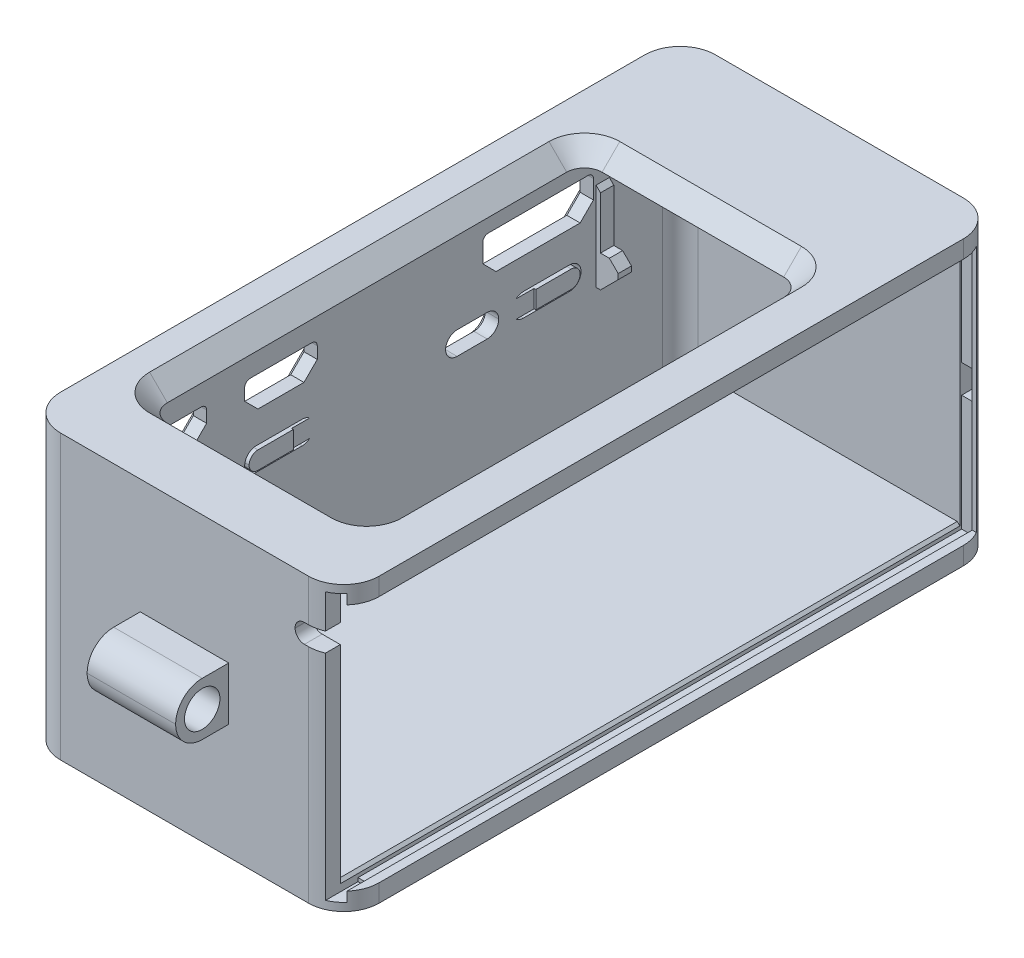
SolidWorks part; units mm, degrees
ref_plane "前视基准面" through (0, 0, 0) normal (0, 0, 1) x (1, 0, 0)
ref_plane "上视基准面" through (0, 0, 0) normal (0, 1, 0) x (1, 0, 0)
ref_plane "右视基准面" through (0, 0, 0) normal (1, 0, 0) x (0, 0, -1)
sketch "草图1" plane through (0, 0, 0) normal (1, 0, 0) x (0, 0, -1)
  line L1 (-54.0501, 29.0398) -> (19.9499, 29.0398)
  line L2 (-54.0501, 29.0398) -> (-54.0501, -2.9602)
  line L3 (-54.0501, -2.9602) -> (19.9499, -2.9602)
  line L4 (19.9499, 29.0398) -> (19.9499, -2.9602)
  dimension "D1" = 74
  dimension "D2" = 32
extrude "凸台-拉伸1" add sketch "草图1" along normal blind 36
sketch "草图2" plane through (36, 0, 0) normal (1, 0, 0) x (0, 0, -1)
  line L8 (17.9499, -0.9602) -> (17.9499, 27.0398)
  line L9 (-52.0501, -0.9602) -> (17.9499, -0.9602)
  line L10 (-52.0501, 27.0398) -> (-52.0501, -0.9602)
  line L11 (17.9499, 27.0398) -> (-52.0501, 27.0398)
  line L12 (17.9499, -0.9602) -> (17.9499, 27.0398)
  line L13 (-52.0501, -0.9602) -> (17.9499, -0.9602)
  line L14 (-52.0501, 27.0398) -> (-52.0501, -0.9602)
  line L15 (17.9499, 27.0398) -> (-52.0501, 27.0398)
  dimension "D1" = 2
extrude "切除-拉伸1" cut sketch "草图2" against normal blind 34
fillet "圆角1" radius 2 2 edges at (2, 13.0398, -17.9499) (2, 13.0398, 52.0501)
fillet "圆角2" radius 4 4 edges at (0, 13.0398, -19.9499) (0, 13.0398, 54.0501) (36, 13.0398, 54.0501) (36, 13.0398, -19.9499)
sketch "草图3" plane through (0, 29.0398, 0) normal (0, 1, 0) x (1, 0, 0)
  line L0 (32, 19.9499) -> (4, 19.9499) construction
  line L1 (29.59, 4.0599) -> (5.07, 4.0599)
  line L2 (29.59, 4.0599) -> (29.59, -45.0601)
  line L3 (29.59, -45.0601) -> (5.07, -45.0601)
  line L4 (5.07, 4.0599) -> (5.07, -45.0601)
  line L5 (36, 15.9499) -> (36, -50.0501) construction
  line L6 (32, -54.0501) -> (4, -54.0501) construction
  line L7 (0, 15.9499) -> (0, -50.0501) construction
  dimension "D1" = 15.89
  dimension "D2" = 6.41
  dimension "D3" = 8.99
  dimension "D4" = 5.07
extrude "切除-拉伸2" cut sketch "草图3" against normal blind 10
fillet "圆角3" radius 2 4 edges at (5.07, 28.0398, 45.0601) (29.59, 28.0398, 45.0601) (29.59, 28.0398, -4.0599) (5.07, 28.0398, -4.0599)
chamfer "倒角1" distance 2 angle 45 8 edges at (17.33, 29.0398, 45.0601) (29.0042, 29.0398, 44.4744) (5.6558, 29.0398, 44.4744) (29.59, 29.0398, 20.5001) (5.07, 29.0398, 20.5001) (29.0042, 29.0398, -3.4741) (5.6558, 29.0398, -3.4741) (17.33, 29.0398, -4.0599)
sketch "草图4" plane through (0, 0, 0) normal (-1, 0, 0) x (0, 0, 1)
  line L0 (-15.9499, 29.0398) -> (50.0501, 29.0398) construction
  line L1 (-8.1499, 22.4398) -> (4.3501, 22.4398)
  line L2 (-8.1499, 22.4398) -> (-8.1499, 18.2398)
  line L3 (-8.1499, 18.2398) -> (4.3501, 18.2398)
  line L4 (4.3501, 22.4398) -> (4.3501, 18.2398)
  line L5 (23.0501, 21.6812) -> (31.2501, 21.6812)
  line L6 (23.0501, 21.6812) -> (23.0501, 18.2398)
  line L7 (23.0501, 18.2398) -> (31.2501, 18.2398)
  line L8 (31.2501, 21.6812) -> (31.2501, 18.2398)
  line L9 (35.5501, 21.6398) -> (43.7501, 21.6398)
  line L10 (35.5501, 21.6398) -> (35.5501, 18.2398)
  line L11 (35.5501, 18.2398) -> (43.7501, 18.2398)
  line L12 (43.7501, 21.6398) -> (43.7501, 18.2398)
  line L13 (-6.7499, 14.7398) -> (1.0501, 14.7398)
  line L14 (-6.7499, 14.7398) -> (-6.7499, 12.1398)
  line L15 (-6.7499, 12.1398) -> (1.0501, 12.1398)
  line L16 (1.0501, 14.7398) -> (1.0501, 12.1398)
  line L17 (23.4501, 14.7398) -> (31.2501, 14.7398)
  line L18 (23.4501, 14.7398) -> (23.4501, 12.1398)
  line L19 (23.4501, 12.1398) -> (31.2501, 12.1398)
  line L20 (31.2501, 14.7398) -> (31.2501, 12.1398)
  line L21 (33.8696, 14.7398) -> (43.3696, 14.7398)
  line L22 (33.8696, 14.7398) -> (33.8696, 11.5398)
  line L23 (33.8696, 11.5398) -> (43.3696, 11.5398)
  line L24 (43.3696, 14.7398) -> (43.3696, 11.5398)
  line L25 (54.0501, 29.0398) -> (54.0501, -2.9602) construction
  line L27 (8.5501, 14.7398) -> (2.5501, 14.7398)
  line L28 (8.5501, 14.7398) -> (8.5501, 12.1398)
  line L29 (8.5501, 12.1398) -> (2.5501, 12.1398)
  line L30 (2.5501, 14.7398) -> (2.5501, 12.1398)
  dimension "D1" = 14.3
  dimension "D2" = 3.2
  dimension "D3" = 2.6
  dimension "D4" = 7.8
  dimension "D5" = 7.8
  dimension "D6" = 8.2
  dimension "D7" = 8.2
  dimension "D8" = 3.4
  dimension "D9" = 12.5
  dimension "D10" = 4.2
  dimension "D11" = 10.8
  dimension "D12" = 10.3
  dimension "D13" = 4.3
  dimension "D14" = 18.7
  dimension "D15" = 9.5
  dimension "D16" = 53
  dimension "D17" = 1.5
  dimension "D18" = 6
extrude "切除-拉伸3" cut sketch "草图4" against normal blind 10
fillet "圆角8" radius 1.3 4 edges at (1, 14.7398, 2.5501) (1, 14.7398, 8.5501) (1, 12.1398, 8.5501) (1, 12.1398, 2.5501)
sketch "草图5" plane through (2, 0, 0) normal (1, 0, 0) x (0, 0, -1)
  line L0 (-23.4501, 12.1398) -> (-23.4501, 14.7398) construction
  line L1 (-23.4501, 14.4398) -> (-30.9501, 14.4398)
  line L2 (-23.4501, 14.4398) -> (-23.4501, 12.4398)
  line L3 (-23.4501, 12.4398) -> (-30.9501, 12.4398)
  line L4 (-30.9501, 14.4398) -> (-30.9501, 12.4398)
  line L5 (-1.0501, 14.7398) -> (-1.0501, 12.1398) construction
  line L6 (-1.0501, 12.4398) -> (6.4499, 12.4398)
  line L7 (-1.0501, 12.4398) -> (-1.0501, 14.4398)
  line L8 (-1.0501, 14.4398) -> (6.4499, 14.4398)
  line L9 (6.4499, 12.4398) -> (6.4499, 14.4398)
  line L10 (-23.4501, 14.7398) -> (-31.2501, 14.7398) construction
  line L11 (-31.2501, 12.1398) -> (-23.4501, 12.1398) construction
  line L12 (-31.2501, 14.7398) -> (-31.2501, 12.1398) construction
  line L13 (6.7499, 14.7398) -> (-1.0501, 14.7398) construction
  line L14 (-1.0501, 12.1398) -> (6.7499, 12.1398) construction
  line L15 (6.7499, 12.1398) -> (6.7499, 14.7398) construction
  dimension "D1" = 0.3
  dimension "D2" = 0.3
  dimension "D3" = 0.3
  dimension "D4" = 0.3
  dimension "D5" = 0.3
  dimension "D6" = 0.3
extrude "凸台-拉伸2" add sketch "草图5" against normal blind 1.2
sketch "草图6" plane through (0.8, 0, 0) normal (-1, 0, 0) x (0, 0, 1)
  line L0 (1.0501, 12.4398) -> (-6.4499, 12.4398) construction
  line L1 (-6.4499, 14.4398) -> (-1.4499, 14.4398)
  line L2 (-6.4499, 14.4398) -> (-6.4499, 12.4398)
  line L3 (-6.4499, 12.4398) -> (-1.4499, 12.4398)
  line L4 (-1.4499, 14.4398) -> (-1.4499, 12.4398)
  line L5 (30.9501, 12.4398) -> (23.4501, 12.4398) construction
  line L6 (30.9501, 14.4398) -> (25.9501, 14.4398)
  line L7 (30.9501, 14.4398) -> (30.9501, 12.4398)
  line L8 (30.9501, 12.4398) -> (25.9501, 12.4398)
  line L9 (25.9501, 14.4398) -> (25.9501, 12.4398)
  dimension "D1" = 5
  dimension "D2" = 5
extrude "凸台-拉伸3" add sketch "草图6" along normal blind 1.5 and the other way blind 1.4
fillet "圆角4" radius 0.6 10 edges at (1, 11.5398, 33.8696) (1, 14.7398, 33.8696) (1, 14.7398, 43.3696) (1, 11.5398, 43.3696) (1, 21.6398, 35.5501) (1, 21.6398, 43.7501) (1, 21.6812, 31.2501) (1, 21.6812, 23.0501) (1, 22.4398, -8.1499) (1, 22.4398, 4.3501)
chamfer "倒角2" distance 1.5 angle 45 6 edges at (1, 18.2398, 43.7501) (1, 18.2398, 35.5501) (1, 18.2398, 31.2501) (1, 18.2398, 23.0501) (1, 18.2398, 4.3501) (1, 18.2398, -8.1499)
fillet "圆角5" radius 1 8 edges at (0.05, 12.4398, 25.9501) (0.05, 14.4398, 25.9501) (0.75, 12.4398, 30.9501) (0.75, 14.4398, 30.9501) (0.05, 12.4398, -1.4499) (0.05, 14.4398, -1.4499) (0.75, 12.4398, -6.4499) (0.75, 14.4398, -6.4499)
chamfer "倒角10" distance 0.2 angle 45 12 edges at (-0.7, 12.4398, 28.4501) (-0.7, 12.7327, 30.6572) (-0.7, 12.7327, 26.243) (-0.7, 14.1469, 30.6572) (-0.7, 14.1469, 26.243) (-0.7, 14.4398, 28.4501) (-0.7, 12.4398, -3.9499) (-0.7, 12.7327, -1.7428) (-0.7, 12.7327, -6.157) (-0.7, 14.1469, -1.7428) (-0.7, 14.1469, -6.157) (-0.7, 14.4398, -3.9499)
fillet "圆角6" radius 1.3 8 edges at (1, 14.7398, 1.0501) (1, 12.1398, 1.0501) (1, 12.1398, -6.7499) (1, 14.7398, -6.7499) (1, 14.7398, 23.4501) (1, 12.1398, 23.4501) (1, 12.1398, 31.2501) (1, 14.7398, 31.2501)
chamfer "倒角4" distance 0.5 angle 45 50 edges at (0, 12.1398, -2.8499) (0, 12.5206, 0.6694) (0, 12.5206, -6.3691) (0, 14.359, 0.6694) (0, 14.359, -6.3691) (0, 14.7398, -2.8499) (0, 18.9898, -7.3999) (0, 18.2398, -1.8999) (0, 18.9898, 3.6001) (0, 20.7898, 4.3501) (0, 20.7898, -8.1499) (0, 22.2641, 4.1744) (0, 22.2641, -7.9741) (0, 22.4398, -1.8999) (0, 11.5398, 38.6196) (0, 11.7155, 43.1938) (0, 11.7155, 34.0453) (0, 13.1398, 43.3696) (0, 13.1398, 33.8696) (0, 14.5641, 43.1938) (0, 14.5641, 34.0453) (0, 14.7398, 38.6196) (0, 12.1398, 27.3501) (0, 12.5206, 30.8694) (0, 12.5206, 23.8309) (0, 14.359, 30.8694) (0, 14.359, 23.8309) (0, 14.7398, 27.3501) (0, 20.4105, 23.0501) (0, 21.5055, 23.2259) (0, 21.6812, 27.1501) (0, 21.5055, 31.0744) (0, 18.9898, 23.8001) (0, 18.2398, 27.1501) (0, 18.9898, 30.5001) (0, 20.4105, 31.2501) (0, 18.9898, 43.0001) (0, 18.2398, 39.6501) (0, 18.9898, 36.3001) (0, 20.3898, 35.5501) (0, 21.4641, 35.7259) (0, 21.6398, 39.6501) (0, 20.3898, 43.7501) (0, 21.4641, 43.5744) (0, 12.5206, 8.1694) (0, 12.1398, 5.5501) (0, 12.5206, 2.9309) (0, 14.359, 8.1694) (0, 14.7398, 5.5501) (0, 14.359, 2.9309)
sketch "草图7" plane through (2, 0, 0) normal (1, 0, 0) x (0, 0, -1)
  line L0 (15.9499, 27.0398) -> (-50.0501, 27.0398) construction
  line L1 (-46.0501, 21.0398) -> (-44.5501, 21.0398)
  line L2 (-46.0501, 21.0398) -> (-46.0501, 11.0398)
  line L3 (-46.0501, 11.0398) -> (-44.5501, 11.0398)
  line L4 (-44.5501, 21.0398) -> (-44.5501, 11.0398)
  line L5 (8.4499, 21.0398) -> (9.9499, 21.0398)
  line L6 (8.4499, 21.0398) -> (8.4499, 11.0398)
  line L7 (8.4499, 11.0398) -> (9.9499, 11.0398)
  line L8 (9.9499, 21.0398) -> (9.9499, 11.0398)
  line L11 (17.9499, -0.9602) -> (17.9499, 27.0398) construction
  line L12 (-52.0501, 27.0398) -> (-52.0501, -0.9602) construction
  dimension "D1" = 6
  dimension "D2" = 10
  dimension "D3" = 1.5
  dimension "D4" = 1.5
  dimension "D5" = 8
  dimension "D6" = 6
extrude "凸台-拉伸4" add sketch "草图7" along normal blind 0.5
sketch "草图10" plane through (2.5, 0, 0) normal (1, 0, 0) x (0, 0, -1)
  line L1 (-46.0501, 11.0398) -> (-44.5501, 11.0398)
  line L2 (-46.0501, 11.0398) -> (-46.0501, 14.6398)
  line L3 (-46.0501, 14.6398) -> (-44.5501, 14.6398)
  line L4 (-44.5501, 11.0398) -> (-44.5501, 14.6398)
  line L7 (8.4499, 11.0398) -> (9.9499, 11.0398)
  line L8 (8.4499, 11.0398) -> (8.4499, 14.6398)
  line L9 (8.4499, 14.6398) -> (9.9499, 14.6398)
  line L10 (9.9499, 11.0398) -> (9.9499, 14.6398)
  dimension "D1" = 3.6
extrude "凸台-拉伸6" add sketch "草图10" along normal blind 2
chamfer "倒角7" distance 1 angle 45 2 edges at (4.5, 14.6398, -9.1999) (4.5, 14.6398, 45.3001)
chamfer "倒角8" distance 2 angle 45 2 edges at (4.5, 11.0398, 45.3001) (4.5, 11.0398, -9.1999)
chamfer "倒角5" distance 0.5 angle 45 2 edges at (2.5, 21.0398, 45.3001) (2.5, 21.0398, -9.1999)
sketch "草图8" plane through (2, 0, 0) normal (1, 0, 0) x (0, 0, -1)
  line L1 (-52.0501, 22.2398) -> (-48.0501, 22.2398)
  line L2 (-52.0501, 22.2398) -> (-52.0501, 24.2398)
  line L3 (-52.0501, 24.2398) -> (-48.0501, 24.2398)
  line L4 (-48.0501, 22.2398) -> (-48.0501, 24.2398)
  line L6 (17.9499, 24.2398) -> (11.9499, 24.2398)
  line L7 (17.9499, 24.2398) -> (17.9499, 22.2398)
  line L8 (17.9499, 22.2398) -> (11.9499, 22.2398)
  line L9 (11.9499, 24.2398) -> (11.9499, 22.2398)
  line L10 (15.9499, 27.0398) -> (-50.0501, 27.0398) construction
  line L11 (17.9499, -0.9602) -> (17.9499, 27.0398) construction
  line L12 (-52.0501, 27.0398) -> (-52.0501, -0.9602) construction
  dimension "D1" = 2.8
  dimension "D2" = 2
  dimension "D3" = 4
  dimension "D4" = 6
extrude "凸台-拉伸5" add sketch "草图8" along normal blind 3
chamfer "倒角6" distance 1 angle 45 2 edges at (5, 24.2398, -14.9499) (5, 24.2398, 50.0501)
sketch "草图12" plane through (0, 0, 54.0501) normal (0, 0, 1) x (1, 0, 0)
  line L0 (4, -0.9602) -> (35.4641, -0.9602) construction
  line L1 (36, 27.0398) -> (33.6, 27.0398)
  line L2 (36, 27.0398) -> (36, -0.9602)
  line L3 (36, -0.9602) -> (33.6, -0.9602)
  line L4 (33.6, 27.0398) -> (33.6, -0.9602)
  dimension "D1" = 2.4
extrude "切除-拉伸5" cut sketch "草图12" against normal blind 10.8
sketch "草图11" plane through (0, -0.9602, 0) normal (0, 1, 0) x (1, 0, 0)
  line L0 (32, 19.9499) -> (4, 19.9499) construction
  line L1 (35, 17.9499) -> (33.6, 17.9499)
  line L2 (35, 17.9499) -> (35, -54.0501)
  line L3 (35, -54.0501) -> (33.6, -54.0501)
  line L4 (33.6, 17.9499) -> (33.6, -54.0501)
  line L5 (32, -54.0501) -> (4, -54.0501) construction
  line L6 (36, -50.0501) -> (36, 15.9499) construction
  dimension "D1" = 2
  dimension "D2" = 0
  dimension "D3" = 1
  dimension "D4" = 1.4
extrude "切除-拉伸4" cut sketch "草图11" against normal blind 0.7
sketch "草图13" plane through (0, 27.0398, 0) normal (0, -1, 0) x (1, 0, 0)
  line L10 (33.6, -17.9499) -> (35, -17.9499)
  line L11 (33.6, 54.0501) -> (33.6, -17.9499)
  line L12 (35, 54.0501) -> (33.6, 54.0501)
  line L13 (35, -17.9499) -> (35, 54.0501)
  line L14 (33.6, -17.9499) -> (35, -17.9499)
  line L15 (33.6, 54.0501) -> (33.6, -17.9499)
  line L16 (35, 54.0501) -> (33.6, 54.0501)
  line L17 (35, -17.9499) -> (35, 54.0501)
  dimension "D1" = 0
extrude "切除-拉伸6" cut sketch "草图13" against normal blind 0.7
sketch "草图14" plane through (0, -1.6602, 0) normal (0, 1, 0) x (1, 0, 0)
  line L1 (33.6, -54.0501) -> (35, -54.0501)
  line L2 (33.6, -54.0501) -> (33.6, -50.0501)
  line L3 (33.6, -50.0501) -> (35, -50.0501)
  line L4 (35, -54.0501) -> (35, -50.0501)
  line L5 (32, -54.0501) -> (4, -54.0501) construction
  line L6 (33.6, -53.7162) -> (33.6, 17.9499) construction
  dimension "D1" = 4
extrude "切除-拉伸7" cut sketch "草图14" against normal blind 0.4
sketch "草图15" plane through (0, 27.7398, 0) normal (0, -1, 0) x (1, 0, 0)
  line L3 (35, 50.0501) -> (35, 52.6959)
  line L4 (33.6, 50.0501) -> (35, 50.0501)
  line L5 (33.6, 53.7162) -> (33.6, 50.0501)
  line L7 (33.6, 50.0501) -> (35, 50.0501)
  line L8 (33.6, 53.7162) -> (33.6, 50.0501)
  line L10 (35, 50.0501) -> (35, 52.6959)
  arc A1 (35, 52.6959) -> (33.6, 53.7162) centre (32, 50.0501) ccw
  arc A2 (35, 52.6959) -> (33.6, 53.7162) centre (32, 50.0501) ccw
  dimension "D1" = 0
extrude "切除-拉伸8" cut sketch "草图15" against normal blind 0.4
sketch "草图16" plane through (0, 0, -17.9499) normal (0, 0, 1) x (1, 0, 0)
  line L0 (33.6, 28.1398) -> (33.6, -2.0602) construction
  line L1 (33.6, 27.7398) -> (35, 27.7398)
  line L2 (33.6, 27.7398) -> (33.6, -1.6602)
  line L3 (33.6, -1.6602) -> (35, -1.6602)
  line L4 (35, 27.7398) -> (35, -1.6602)
extrude "切除-拉伸9" cut sketch "草图16" against normal blind 0.2
chamfer "倒角9" distance 0.3 angle 45 2 edges at (33.6, 27.0398, 17.0501) (33.6, -0.9602, 17.0501)
ref_plane "基准面4" through (0, 13.0398, 0) normal (0, -1, 0) x (-1, 0, 0)
sketch "草图19" plane through (0, 0, -18.1499) normal (0, 0, 1) x (1, 0, 0)
  line L0 (35, 13.0398) -> (40.512, 13.0398) construction
  line L1 (35.4641, -0.9602) -> (35.4641, 27.0398) construction
  line L3 (34.3, 27.7398) -> (34.3, 24.7272) construction
  line L4 (33.6, 27.7398) -> (35, 27.7398) construction
  line L5 (35, -0.9602) -> (35, 27.0398) construction
  line L6 (33.6, 14.6398) -> (35, 14.6398)
  line L7 (33.6, 14.6398) -> (33.6, 11.4398)
  line L8 (33.6, 11.4398) -> (35, 11.4398)
  line L9 (35, 14.6398) -> (35, 11.4398)
  line L10 (33.6, 14.6398) -> (35, 11.4398) construction
  line L11 (33.6, 11.4398) -> (35, 14.6398) construction
  point P2 (34.3, 13.0398)
  point P13 (35.4641, 13.0398)
  point P16 (34.3, 27.7398)
  dimension "D1" = 3.2
extrude "切除-拉伸11" cut sketch "草图19" against normal blind 10
sketch "草图20" plane through (0, 0, 54.0501) normal (0, 0, 1) x (1, 0, 0)
  line L0 (33.6, 24.2398) -> (33.6, 28.1198) construction
  line L1 (33.6, 24.2898) -> (30.5, 24.2898)
  line L2 (33.6, 24.2898) -> (33.6, 22.1398)
  line L3 (33.6, 22.1398) -> (30.5, 22.1398)
  line L4 (30.5, 24.2898) -> (30.5, 22.1398)
  line L5 (32, 29.0398) -> (4, 29.0398) construction
  dimension "D1" = 4.75
  dimension "D2" = 2.15
  dimension "D3" = 3.1
extrude "切除-拉伸12" cut sketch "草图20" against normal up to next
fillet "圆角9" radius 1.05 2 edges at (30.5, 24.2898, 53.0501) (30.5, 22.1398, 53.0501)
sketch "草图21" plane through (0, 0, -19.9499) normal (0, 0, -1) x (-1, 0, 0)
  line L0 (-25, 19.5398) -> (-14, 19.5398) construction
  line L1 (-25, 21.0398) -> (-14, 21.0398)
  line L2 (-25, 18.0398) -> (-14, 18.0398)
  line L3 (-4, -2.9602) -> (-4, 29.0398) construction
  line L4 (-32, 29.0398) -> (-4, 29.0398) construction
  arc A0 (-25, 21.0398) -> (-25, 18.0398) centre (-25, 19.5398) ccw
  arc A1 (-14, 18.0398) -> (-14, 21.0398) centre (-14, 19.5398) ccw
  point P2 (-19.5, 19.5398)
  dimension "D4" = 1.5
  dimension "D1" = 10
  dimension "D2" = 9.5
  dimension "D3" = 11
extrude "切除-拉伸13" cut sketch "草图21" against normal up to next
sketch "草图22" plane through (0, -2.9602, 0) normal (0, -1, 0) x (1, 0, 0)
  line L0 (7.07, -6.0599) -> (27.59, -6.0599) construction
  line B0 (12.438, 7.4573) -> (11.965, 6.6368)
  line B1 (11.965, 6.6368) -> (9.5089, 2.3799)
  line B2 (9.5089, 2.3799) -> (9.0302, 1.5593)
  line B3 (9.0302, -0.1617) -> (9.5089, -0.9823)
  line B4 (9.5089, -0.9823) -> (11.965, -5.2392)
  line B5 (11.965, -5.2392) -> (12.438, -6.0599)
  line B6 (13.9253, -6.9204) -> (20.7409, -6.9204)
  line B7 (22.2283, -6.0599) -> (22.7013, -5.2392)
  line B8 (22.7013, -5.2392) -> (25.1574, -0.9823)
  line B9 (25.1574, -0.9823) -> (25.6361, -0.1617)
  line B10 (25.6361, 1.5593) -> (25.1574, 2.3799)
  line B11 (25.1574, 2.3799) -> (22.7013, 6.6368)
  line B12 (22.7013, 6.6368) -> (22.2283, 7.4573)
  line B13 (20.7409, 8.3178) -> (13.9253, 8.3178)
  line B14 (13.1161, -4.9657) -> (10.073, 0.2999)
  line B15 (10.073, 1.1034) -> (13.1218, 6.3404)
  line B16 (13.8228, 6.3461) -> (16.8658, 1.2573)
  line B17 (22.0231, 2.8358) -> (22.3536, 2.2431)
  line B18 (22.4505, 2.1861) -> (24.1601, 2.1861)
  line B19 (24.257, 2.1292) -> (24.8838, 1.0236)
  line B20 (24.787, 0.8583) -> (19.51, 0.8583)
  line B21 (19.4131, 0.9153) -> (18.3475, 2.7959)
  line B22 (21.6698, 6.7393) -> (22.291, 5.6452)
  line B23 (22.1941, 5.4799) -> (19.681, 5.4799)
  line B24 (19.5841, 5.537) -> (18.9686, 6.6311)
  line B25 (19.0655, 6.7963) -> (21.5729, 6.7963)
  line B26 (21.0088, 2.7674) -> (21.2709, 2.2431)
  line B27 (21.1512, 2.1861) -> (19.8064, 2.1861)
  line B28 (19.7095, 2.2431) -> (19.4359, 2.7332)
  line B29 (14.404, 12.3126) -> (14.404, 10.4377)
  line B30 (14.404, 10.4377) -> (20.9689, 10.4377)
  line B31 (20.9689, 10.4377) -> (20.9689, 11.2698)
  line B32 (20.9689, 11.2698) -> (18.3646, 11.2698)
  line B33 (18.3646, 11.2698) -> (18.3646, 12.3582)
  line B34 (17.6921, 12.25) -> (17.6921, 11.2698)
  line B35 (17.6921, 11.2698) -> (15.0765, 11.2698)
  line B36 (15.0765, 11.2698) -> (15.0765, 12.2158)
  line B37 (16.1022, 15.8514) -> (20.9689, 15.8514)
  line B38 (20.9689, 15.8514) -> (20.9689, 16.6665)
  line B39 (20.9689, 16.6665) -> (16.1022, 16.6665)
  line B40 (16.1022, 16.6665) -> (16.1022, 15.8514)
  line B41 (17.1793, 21.3735) -> (16.8487, 20.5415)
  line B42 (16.0623, 21.6983) -> (15.0594, 22.4962)
  line B43 (18.0227, 19.265) -> (18.3817, 20.1141)
  line B44 (19.0313, 18.564) -> (20.1369, 17.658)
  line B45 (15.8743, 26.4795) -> (19.2137, 26.4795)
  line B46 (18.8262, 25.0377) -> (15.8743, 25.0377)
  line B47 (15.8743, 25.0377) -> (15.8743, 23.4478)
  line B48 (15.8743, 23.4478) -> (19.0256, 23.4478)
  line B49 (20.2679, 26.6277) -> (20.2679, 26.6618)
  line B50 (20.2679, 26.6618) -> (20.9689, 26.7759)
  line B51 (20.9689, 26.7759) -> (20.9689, 28.0751)
  line B52 (20.9689, 28.0751) -> (15.8743, 28.0751)
  line B53 (15.8743, 28.0751) -> (15.8743, 26.4795)
  line B54 (19.9659, 31.9274) -> (19.9659, 31.1239)
  line B55 (17.0254, 33.0216) -> (17.0254, 33.8079)
  line B56 (17.0254, 33.8079) -> (15.8743, 33.8079)
  line B57 (15.8743, 33.8079) -> (15.8743, 31.9388)
  line B58 (18.9174, 29.6878) -> (18.9516, 29.6878)
  line B59 (20.7808, 29.591) -> (20.8264, 29.591)
  line B60 (21.1854, 31.141) -> (21.1854, 31.6254)
  line B61 (16.4156, 34.2638) -> (17.4642, 34.8223)
  line B62 (20.456, 37.0676) -> (20.456, 37.1075)
  line B63 (20.456, 37.1075) -> (20.9689, 37.2214)
  line B64 (20.9689, 37.2214) -> (20.9689, 38.5207)
  line B65 (20.9689, 38.5207) -> (18.074, 38.5207)
  line B66 (18.6381, 36.9251) -> (19.453, 36.9251)
  line B67 (16.7576, 41.0111) -> (16.7576, 40.9769)
  line B68 (16.7576, 40.9769) -> (15.8743, 40.8686)
  line B69 (15.8743, 40.8686) -> (15.8743, 39.5693)
  line B70 (15.8743, 39.5693) -> (20.9689, 39.5693)
  line B71 (20.9689, 39.5693) -> (20.9689, 41.1536)
  line B72 (20.9689, 41.1536) -> (18.0569, 41.1536)
  line B73 (17.2248, 42.8118) -> (15.8515, 43.0796)
  line B74 (21.2709, 2.2431) -> (22.3536, 2.2431)
  line B75 (21.1512, 2.1861) -> (22.4505, 2.1861)
  spline B76 degree 3 poles (9.0302, 1.5593) (8.882, 1.2914) (8.8022, 0.9951) (8.8022, 0.6988) knots 3 3 3 3 4 4 4 4
  spline B77 degree 3 poles (8.8022, 0.6988) (8.8022, 0.4025) (8.882, 0.1061) (9.0302, -0.1617) knots 4 4 4 4 5 5 5 5
  spline B78 degree 3 poles (12.438, -6.0599) (12.7457, -6.5898) (13.3156, -6.9204) (13.9253, -6.9204) knots 8 8 8 8 9 9 9 9
  spline B79 degree 3 poles (20.7409, -6.9204) (21.3564, -6.9204) (21.9206, -6.5898) (22.2283, -6.0599) knots 10 10 10 10 11 11 11 11
  spline B80 degree 3 poles (25.6361, -0.1617) (25.7899, 0.1061) (25.864, 0.4025) (25.864, 0.6988) knots 14 14 14 14 15 15 15 15
  spline B81 degree 3 poles (25.864, 0.6988) (25.864, 0.9951) (25.7899, 1.2914) (25.6361, 1.5593) knots 15 15 15 15 16 16 16 16
  spline B82 degree 3 poles (22.2283, 7.4573) (21.9206, 7.993) (21.3564, 8.3178) (20.7409, 8.3178) knots 19 19 19 19 20 20 20 20
  spline B83 degree 3 poles (13.9253, 8.3178) (13.3156, 8.3178) (12.7457, 7.993) (12.438, 7.4573) knots 21 21 21 21 22 22 22 22
  spline B84 degree 2 poles (16.8658, 0.146) (13.8911, -5.0056) (13.8854, -5.017) knots 0 0 0 1 1 1
  spline B85 degree 3 poles (13.8854, -5.017) (13.6917, -5.2848) (13.2814, -5.2563) (13.1161, -4.9657) knots 1 1 1 1 2 2 2 2
  spline B86 degree 3 poles (10.073, 0.2999) (9.9306, 0.5449) (9.9306, 0.8527) (10.073, 1.1034) knots 3 3 3 3 4 4 4 4
  spline B87 degree 3 poles (13.1218, 6.3404) (13.2757, 6.6082) (13.6632, 6.6139) (13.8228, 6.3461) knots 5 5 5 5 6 6 6 6
  spline B88 degree 3 poles (16.8658, 1.2573) (17.0653, 0.9153) (17.0653, 0.4879) (16.8658, 0.146) knots 7 7 7 7 8 8 8 8
  spline B89 degree 3 poles (24.1601, 2.1861) (24.2, 2.1861) (24.2342, 2.169) (24.257, 2.1292) knots 3 3 3 3 4 4 4 4
  spline B90 degree 3 poles (24.8838, 1.0236) (24.9237, 0.9495) (24.8725, 0.8583) (24.787, 0.8583) knots 5 5 5 5 6 6 6 6
  spline B91 degree 3 poles (19.51, 0.8583) (19.4701, 0.8583) (19.4302, 0.8754) (19.4131, 0.9153) knots 7 7 7 7 8 8 8 8
  spline B92 degree 3 poles (18.3475, 2.7959) (17.6579, 4.0154) (17.5212, 5.024) (18.8889, 5.024) knots 9 9 9 9 10 10 10 10
  spline B93 degree 3 poles (18.8889, 5.024) (20.2053, 5.024) (21.3621, 4.004) (22.0231, 2.8358) knots 10 10 10 10 11 11 11 11
  spline B94 degree 3 poles (21.5729, 6.7963) (21.6128, 6.7963) (21.6527, 6.7735) (21.6698, 6.7393) knots 0 0 0 0 1 1 1 1
  spline B95 degree 3 poles (22.291, 5.6452) (22.3309, 5.5711) (22.2795, 5.4799) (22.1941, 5.4799) knots 2 2 2 2 3 3 3 3
  spline B96 degree 3 poles (19.681, 5.4799) (19.6411, 5.4799) (19.6069, 5.5027) (19.5841, 5.537) knots 4 4 4 4 5 5 5 5
  spline B97 degree 3 poles (18.9686, 6.6311) (18.9288, 6.7051) (18.98, 6.7963) (19.0655, 6.7963) knots 6 6 6 6 7 7 7 7
  spline B98 degree 3 poles (17.2989, 6.141) (17.0482, 6.5798) (17.1565, 6.8932) (17.5554, 6.8932) (17.9486, 6.8932) (18.4102, 6.5798) (18.6552, 6.141) knots 2 2 2 2 3 3 3 4 4 4 4
  spline B99 degree 3 poles (18.6552, 6.141) (18.9117, 5.6965) (18.8034, 5.3831) (18.4102, 5.3831) (18.0056, 5.3831) (17.5497, 5.6965) (17.2989, 6.141) knots 0 0 0 0 1 1 1 2 2 2 2
  spline B100 degree 3 poles (19.624, 3.7248) (20.1654, 3.7248) (20.644, 3.4171) (21.0088, 2.7674) knots 0 0 0 0 1 1 1 1
  spline B101 degree 3 poles (19.8064, 2.1861) (19.7665, 2.1861) (19.7266, 2.2089) (19.7095, 2.2431) knots 4 4 4 4 5 5 5 5
  spline B102 degree 3 poles (19.4359, 2.7332) (19.0712, 3.3714) (19.0655, 3.7248) (19.624, 3.7248) knots 6 6 6 6 7 7 7 7
  spline B103 degree 3 poles (18.3646, 12.3582) (18.3646, 13.7886) (17.715, 14.7745) (16.3302, 14.7745) knots 5 5 5 5 6 6 6 6
  spline B104 degree 3 poles (16.3302, 14.7745) (14.8941, 14.7745) (14.404, 13.7886) (14.404, 12.3126) knots 6 6 6 6 7 7 7 7
  spline B105 degree 3 poles (15.0765, 12.2158) (15.0765, 13.3669) (15.3785, 13.9482) (16.3302, 13.9482) knots 3 3 3 3 4 4 4 4
  spline B106 degree 3 poles (16.3302, 13.9482) (17.2704, 13.9482) (17.6921, 13.4068) (17.6921, 12.25) knots 4 4 4 4 5 5 5 5
  spline B107 degree 3 poles (15.0993, 16.2618) (15.0993, 16.5866) (14.877, 16.826) (14.575, 16.826) (14.2388, 16.826) (14.045, 16.5866) (14.045, 16.2618) knots 2 2 2 2 3 3 3 4 4 4 4
  spline B108 degree 3 poles (14.045, 16.2618) (14.045, 15.937) (14.2388, 15.6976) (14.575, 15.6976) (14.877, 15.6976) (15.0993, 15.937) (15.0993, 16.2618) knots 0 0 0 0 1 1 1 2 2 2 2
  spline B109 degree 3 poles (16.8487, 20.5415) (16.6151, 19.9545) (16.4726, 19.5328) (16.1022, 19.5328) knots 1 1 1 1 2 2 2 2
  spline B110 degree 3 poles (16.1022, 19.5328) (15.7489, 19.5328) (15.5494, 19.8349) (15.5494, 20.3306) knots 2 2 2 2 3 3 3 3
  spline B111 degree 3 poles (15.5494, 20.3306) (15.5494, 20.8492) (15.7261, 21.2595) (16.0623, 21.6983) knots 3 3 3 3 4 4 4 4
  spline B112 degree 3 poles (15.0594, 22.4962) (14.4724, 21.9149) (14.1761, 21.1) (14.1761, 20.3306) knots 5 5 5 5 6 6 6 6
  spline B113 degree 3 poles (14.1761, 20.3306) (14.1761, 18.9117) (15.0765, 17.9087) (16.1934, 17.9087) knots 6 6 6 6 7 7 7 7
  spline B114 degree 3 poles (16.1934, 17.9087) (17.1622, 17.9087) (17.7434, 18.564) (18.0227, 19.265) knots 7 7 7 7 8 8 8 8
  spline B115 degree 3 poles (18.3817, 20.1141) (18.621, 20.684) (18.7464, 21.0544) (19.1339, 21.0544) knots 9 9 9 9 10 10 10 10
  spline B116 degree 3 poles (19.1339, 21.0544) (19.4929, 21.0544) (19.7152, 20.7752) (19.7152, 20.1825) knots 10 10 10 10 11 11 11 11
  spline B117 degree 3 poles (19.7152, 20.1825) (19.7152, 19.6582) (19.4359, 19.037) (19.0313, 18.564) knots 11 11 11 11 12 12 12 12
  spline B118 degree 3 poles (20.1369, 17.658) (20.7694, 18.3475) (21.0943, 19.282) (21.0943, 20.1483) knots 13 13 13 13 14 14 14 14
  spline B119 degree 3 poles (21.0943, 20.1483) (21.0943, 21.761) (20.1198, 22.6955) (19.0085, 22.6955) knots 14 14 14 14 15 15 15 15
  spline B120 degree 3 poles (19.0085, 22.6955) (18.0683, 22.6955) (17.5098, 22.1998) (17.1793, 21.3735) knots 15 15 15 15 16 16 16 16
  spline B121 degree 3 poles (19.2137, 26.4795) (19.5898, 26.2117) (19.7323, 25.9894) (19.7323, 25.6304) knots 1 1 1 1 2 2 2 2
  spline B122 degree 3 poles (19.7323, 25.6304) (19.7323, 25.2258) (19.5328, 25.0377) (18.8262, 25.0377) knots 2 2 2 2 3 3 3 3
  spline B123 degree 3 poles (19.0256, 23.4478) (20.2964, 23.4478) (21.0943, 23.9208) (21.0943, 25.032) knots 6 6 6 6 7 7 7 7
  spline B124 degree 3 poles (21.0943, 25.032) (21.0943, 25.7273) (20.7694, 26.206) (20.2679, 26.6277) knots 7 7 7 7 8 8 8 8
  spline B125 degree 3 poles (19.9659, 31.1239) (19.9659, 30.5768) (19.8576, 30.3717) (19.624, 30.3717) knots 1 1 1 1 2 2 2 2
  spline B126 degree 3 poles (19.624, 30.3717) (19.453, 30.3717) (19.3732, 30.4115) (19.265, 30.5312) knots 2 2 2 2 3 3 3 3
  spline B127 degree 3 poles (19.265, 30.5312) (19.3276, 30.7535) (19.3562, 30.9586) (19.3562, 31.1296) knots 3 3 3 3 4 4 4 4
  spline B128 degree 3 poles (19.3562, 31.1296) (19.3562, 32.2579) (18.8376, 33.164) (17.6466, 33.164) knots 4 4 4 4 5 5 5 5
  spline B129 degree 3 poles (17.6466, 33.164) (17.4015, 33.164) (17.1679, 33.1013) (17.0254, 33.0216) knots 5 5 5 5 6 6 6 6
  spline B130 degree 3 poles (15.8743, 31.9388) (15.7888, 31.7051) (15.7489, 31.4259) (15.7489, 31.1296) knots 9 9 9 9 10 10 10 10
  spline B131 degree 3 poles (15.7489, 31.1296) (15.7489, 30.0298) (16.353, 28.9983) (17.601, 28.9983) knots 10 10 10 10 11 11 11 11
  spline B132 degree 3 poles (17.601, 28.9983) (18.1936, 28.9983) (18.6666, 29.3288) (18.9174, 29.6878) knots 11 11 11 11 12 12 12 12
  spline B133 degree 3 poles (18.9516, 29.6878) (19.1852, 29.3573) (19.5442, 29.1236) (19.9032, 29.1236) knots 13 13 13 13 14 14 14 14
  spline B134 degree 3 poles (19.9032, 29.1236) (20.3306, 29.1236) (20.5985, 29.3231) (20.7808, 29.591) knots 14 14 14 14 15 15 15 15
  spline B135 degree 3 poles (20.8264, 29.591) (21.0658, 29.1179) (21.4077, 28.8672) (21.8294, 28.8672) knots 16 16 16 16 17 17 17 17
  spline B136 degree 3 poles (21.8294, 28.8672) (22.7411, 28.8672) (23.1116, 29.8303) (23.1116, 31.0042) knots 17 17 17 17 18 18 18 18
  spline B137 degree 3 poles (23.1116, 31.0042) (23.1116, 32.7765) (22.348, 33.8878) (21.2709, 33.8878) knots 18 18 18 18 19 19 19 19
  spline B138 degree 3 poles (21.2709, 33.8878) (20.3477, 33.8878) (19.9659, 33.1811) (19.9659, 31.9274) knots 19 19 19 19 20 20 20 20
  spline B139 degree 3 poles (18.3988, 31.1296) (18.3988, 30.7649) (18.1309, 30.4857) (17.601, 30.4857) (17.0824, 30.4857) (16.8146, 30.7649) (16.8146, 31.1296) knots 2 2 2 2 3 3 3 4 4 4 4
  spline B140 degree 3 poles (16.8146, 31.1296) (16.8146, 31.5057) (17.0824, 31.7735) (17.601, 31.7735) (18.1309, 31.7735) (18.3988, 31.5057) (18.3988, 31.1296) knots 0 0 0 0 1 1 1 2 2 2 2
  spline B141 degree 3 poles (22.1143, 31.2549) (22.1143, 30.5996) (21.9376, 30.1722) (21.5786, 30.1722) knots 0 0 0 0 1 1 1 1
  spline B142 degree 3 poles (21.5786, 30.1722) (21.4077, 30.1722) (21.2652, 30.252) (21.1227, 30.4115) knots 1 1 1 1 2 2 2 2
  spline B143 degree 3 poles (21.1227, 30.4115) (21.1683, 30.5768) (21.1854, 30.7706) (21.1854, 31.141) knots 2 2 2 2 3 3 3 3
  spline B144 degree 3 poles (21.1854, 31.6254) (21.1854, 32.0983) (21.2481, 32.3662) (21.5501, 32.3662) knots 4 4 4 4 5 5 5 5
  spline B145 degree 3 poles (21.5501, 32.3662) (21.875, 32.3662) (22.1143, 31.9104) (22.1143, 31.2549) knots 5 5 5 5 6 6 6 6
  spline B146 degree 3 poles (15.7489, 36.4579) (15.7489, 35.6657) (16.0167, 34.9363) (16.4156, 34.2638) knots 0 0 0 0 1 1 1 1
  spline B147 degree 3 poles (17.4642, 34.8223) (17.1793, 35.3296) (17.0197, 35.7512) (17.0197, 36.1558) knots 2 2 2 2 3 3 3 3
  spline B148 degree 3 poles (17.0197, 36.1558) (17.0197, 36.6744) (17.259, 36.891) (17.6694, 36.9251) knots 3 3 3 3 4 4 4 4
  spline B149 degree 3 poles (17.6694, 36.9251) (17.8859, 34.9363) (18.4671, 34.0928) (19.5442, 34.0928) knots 4 4 4 4 5 5 5 5
  spline B150 degree 3 poles (19.5442, 34.0928) (20.3933, 34.0928) (21.0943, 34.6684) (21.0943, 35.6088) knots 5 5 5 5 6 6 6 6
  spline B151 degree 3 poles (21.0943, 35.6088) (21.0943, 36.1729) (20.8321, 36.6459) (20.456, 37.0676) knots 6 6 6 6 7 7 7 7
  spline B152 degree 3 poles (18.074, 38.5207) (16.4783, 38.5207) (15.7489, 37.7742) (15.7489, 36.4579) knots 11 11 11 11 12 12 12 12
  spline B153 degree 3 poles (19.453, 36.9251) (19.7038, 36.6915) (19.8576, 36.4806) (19.8576, 36.1558) knots 0 0 0 0 1 1 1 1
  spline B154 degree 3 poles (19.8576, 36.1558) (19.8576, 35.8253) (19.7152, 35.6088) (19.4188, 35.6088) knots 1 1 1 1 2 2 2 2
  spline B155 degree 3 poles (19.4188, 35.6088) (19.0598, 35.6088) (18.7749, 35.9336) (18.6381, 36.9251) knots 2 2 2 2 3 3 3 3
  spline B156 degree 3 poles (15.7489, 42.4642) (15.7489, 41.9513) (16.0794, 41.3872) (16.7576, 41.0111) knots 0 0 0 0 1 1 1 1
  spline B157 degree 3 poles (18.0569, 41.1536) (17.3844, 41.4214) (17.1451, 41.8773) (17.1451, 42.2534) knots 7 7 7 7 8 8 8 8
  spline B158 degree 3 poles (17.1451, 42.2534) (17.1451, 42.4813) (17.1793, 42.6295) (17.2248, 42.8118) knots 8 8 8 8 9 9 9 9
  spline B159 degree 3 poles (15.8515, 43.0796) (15.7888, 42.9372) (15.7489, 42.7663) (15.7489, 42.4642) knots 10 10 10 10 11 11 11 11
sketch_block_instance "块1-1"
sketch_block "块1"
extrude "切除-拉伸14" cut sketch "草图22" against normal blind 0.3
ref_plane "基准面5" through (13, 0, 0) normal (1, 0, 0) x (0, 0, -1)
sketch "草图23" plane through (13, 0, 0) normal (1, 0, 0) x (0, 0, -1)
  line L0 (-54.0501, -2.9602) -> (-54.0501, 22.1398) construction
  line L1 (-54.0501, 16.0398) -> (-60.0501, 16.0398)
  line L2 (-54.0501, 16.0398) -> (-54.0501, 10.0398)
  line L3 (-54.0501, 10.0398) -> (-60.0501, 10.0398)
  line L4 (-60.0501, 16.0398) -> (-60.0501, 10.0398)
  dimension "D1" = 13
  dimension "D2" = 6
  dimension "D3" = 6
extrude "凸台-拉伸7" add sketch "草图23" along normal blind 10
sketch "草图24" plane through (23, 0, 0) normal (1, 0, 0) x (0, 0, -1)
  line L0 (-60.0501, 16.0398) -> (-54.0501, 10.0398) construction
  line L2 (-54.0501, -2.9602) -> (-54.0501, 22.1398) construction
  line L3 (-54.0501, 16.0398) -> (-60.0501, 16.0398) construction
  line L4 (-54.0501, 16.0398) -> (-60.0501, 10.0398) construction
  circle A0 centre (-57.0501, 13.0398) radius 2
  dimension "D1" = 4
extrude "切除-拉伸15" cut sketch "草图24" against normal through all
fillet "圆角10" radius 3 2 edges at (18, 10.0398, 60.0501) (18, 16.0398, 60.0501)
